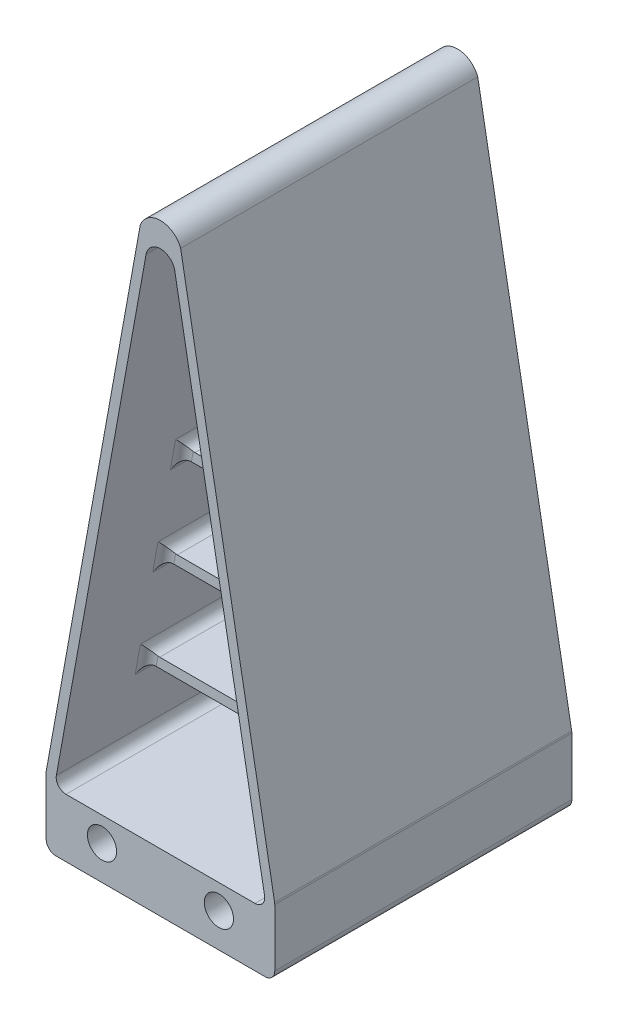
SolidWorks part; units mm, degrees
ref_plane "Front Plane" through (0, 0, 0) normal (0, 0, 1) x (1, 0, 0)
ref_plane "Top Plane" through (0, 0, 0) normal (0, 1, 0) x (1, 0, 0)
ref_plane "Right Plane" through (0, 0, 0) normal (1, 0, 0) x (0, 0, -1)
sketch "Sketch1" plane through (0, 0, 0) normal (0, 0, 1) x (1, 0, 0)
  line L0 (-0.246, 29.2945) -> (-1.0225, 25) construction
  line L1 (1.0225, 25) -> (0.246, 29.2945) construction
  line L2 (-1.0225, 25) -> (1.0225, 25) construction
  line L3 (1.2034, 24) -> (-1.2034, 24) construction
  line L4 (-1.2034, 24) -> (-2.8307, 15) construction
  line L5 (-2.8307, 15) -> (-1.0115, 15) construction
  line L6 (-1.0115, 15) -> (-1.0115, 15.5) construction
  line L7 (-1.0115, 15.5) -> (1.0115, 15.5) construction
  line L8 (2.8307, 15) -> (1.2034, 24) construction
  line L9 (1.0115, 15.5) -> (1.0115, 15) construction
  line L10 (1.0115, 15) -> (2.8307, 15) construction
  line L11 (3.0115, 14) -> (1.0115, 14) construction
  line L12 (1.0115, 14) -> (1.0115, 13.5) construction
  line L13 (1.0115, 13.5) -> (-1.0115, 13.5) construction
  line L14 (-1.0115, 13.5) -> (-1.0115, 14) construction
  line L15 (-1.0115, 14) -> (-3.0115, 14) construction
  line L16 (-3.0115, 14) -> (-4.6389, 5) construction
  line L17 (-4.6389, 5) -> (-2.8197, 5) construction
  line L18 (-2.8197, 5) -> (-2.8197, 5.5) construction
  line L19 (-2.8197, 5.5) -> (2.8197, 5.5) construction
  line L20 (2.8197, 5.5) -> (2.8197, 5) construction
  line L21 (2.8197, 5) -> (4.6389, 5) construction
  line L22 (4.6389, 5) -> (3.0115, 14) construction
  line L23 (4.8197, 4) -> (2.8197, 4) construction
  line L24 (2.8197, 4) -> (2.8197, 3.5) construction
  line L25 (2.8197, 3.5) -> (-2.8197, 3.5) construction
  line L26 (-2.8197, 3.5) -> (-2.8197, 4) construction
  line L27 (-2.8197, 4) -> (-4.8197, 4) construction
  line L28 (-4.8197, 4) -> (-6.4471, -5) construction
  line L29 (-6.4471, -5) -> (-4.6279, -5) construction
  line L30 (-4.6279, -5) -> (-4.6279, -4.5) construction
  line L31 (-4.6279, -4.5) -> (4.6279, -4.5) construction
  line L32 (4.6279, -4.5) -> (4.6279, -5) construction
  line L33 (6.4471, -5) -> (4.8197, 4) construction
  line L34 (4.6279, -5) -> (6.4471, -5) construction
  line L35 (6.6279, -6) -> (4.6279, -6) construction
  line L36 (4.6279, -6) -> (4.6279, -6.5) construction
  line L37 (4.6279, -6.5) -> (-4.6279, -6.5) construction
  line L38 (-4.6279, -6.5) -> (-4.6279, -6) construction
  line L39 (-4.6279, -6) -> (-6.6279, -6) construction
  line L40 (-6.6279, -6) -> (-8.2553, -15) construction
  line L41 (-6.4361, -16) -> (-8.4361, -16) construction
  line L42 (-8.2553, -15) -> (-6.4361, -15) construction
  line L43 (-6.4361, -15) -> (-6.4361, -14.5) construction
  line L44 (-6.4361, -16.5) -> (-6.4361, -16) construction
  line L45 (6.4361, -16.5) -> (-6.4361, -16.5) construction
  line L46 (-6.4361, -14.5) -> (6.4361, -14.5) construction
  line L47 (6.4361, -14.5) -> (6.4361, -15) construction
  line L48 (6.4361, -16) -> (6.4361, -16.5) construction
  line L49 (8.4361, -16) -> (6.4361, -16) construction
  line L50 (8.2553, -15) -> (6.6279, -6) construction
  line L51 (6.4361, -15) -> (8.2553, -15) construction
  line L52 (10.0635, -25) -> (8.4361, -16) construction
  line L53 (9.7018, -23) -> (-9.7018, -23)
  line L54 (2.2141, 29.6504) -> (2.0739, 30.4257)
  line L55 (-2.2141, 29.6504) -> (-2.0739, 30.4257)
  line L56 (0.246, 29.2945) -> (0, 30.655)
  line L57 (-0.246, 29.2945) -> (0, 30.655)
  line L59 (-8.4361, -16) -> (-10.0635, -25) construction
  line L68 (13, -30) -> (2.2141, 29.6504) construction
  line L69 (-2.2141, 29.6504) -> (-13, -30) construction
  line L70 (-0.246, 29.2945) -> (-1.0225, 25)
  line L71 (1.0225, 25) -> (0.246, 29.2945)
  line L72 (-1.0225, 25) -> (1.0225, 25)
  line L73 (1.2034, 24) -> (-1.2034, 24)
  line L74 (-1.2034, 24) -> (-2.8307, 15)
  line L75 (-2.8307, 15) -> (-1.0115, 15)
  line L76 (-1.0115, 15) -> (-1.0115, 15.5)
  line L77 (-1.0115, 15.5) -> (1.0115, 15.5)
  line L78 (2.8307, 15) -> (1.2034, 24)
  line L79 (1.0115, 15.5) -> (1.0115, 15)
  line L80 (1.0115, 15) -> (2.8307, 15)
  line L81 (3.0115, 14) -> (1.0115, 14)
  line L82 (1.0115, 14) -> (1.0115, 13.5)
  line L83 (1.0115, 13.5) -> (-1.0115, 13.5)
  line L84 (-1.0115, 13.5) -> (-1.0115, 14)
  line L85 (-1.0115, 14) -> (-3.0115, 14)
  line L86 (-3.0115, 14) -> (-4.6389, 5)
  line L87 (-4.6389, 5) -> (-2.8197, 5)
  line L88 (-2.8197, 5) -> (-2.8197, 5.5)
  line L89 (-2.8197, 5.5) -> (2.8197, 5.5)
  line L90 (2.8197, 5.5) -> (2.8197, 5)
  line L91 (2.8197, 5) -> (4.6389, 5)
  line L92 (4.6389, 5) -> (3.0115, 14)
  line L93 (4.8197, 4) -> (2.8197, 4)
  line L94 (2.8197, 4) -> (2.8197, 3.5)
  line L95 (2.8197, 3.5) -> (-2.8197, 3.5)
  line L96 (-2.8197, 3.5) -> (-2.8197, 4)
  line L97 (-2.8197, 4) -> (-4.8197, 4)
  line L98 (-4.8197, 4) -> (-6.4471, -5)
  line L99 (-6.4471, -5) -> (-4.6279, -5)
  line L100 (-4.6279, -5) -> (-4.6279, -4.5)
  line L101 (-4.6279, -4.5) -> (4.6279, -4.5)
  line L102 (4.6279, -4.5) -> (4.6279, -5)
  line L103 (6.4471, -5) -> (4.8197, 4)
  line L104 (4.6279, -5) -> (6.4471, -5)
  line L105 (6.6279, -6) -> (4.6279, -6)
  line L106 (4.6279, -6) -> (4.6279, -6.5)
  line L107 (4.6279, -6.5) -> (-4.6279, -6.5)
  line L108 (-4.6279, -6.5) -> (-4.6279, -6)
  line L109 (-4.6279, -6) -> (-6.6279, -6)
  line L110 (-6.6279, -6) -> (-8.2553, -15)
  line L111 (-6.4361, -16) -> (-8.4361, -16)
  line L112 (-8.2553, -15) -> (-6.4361, -15)
  line L113 (-6.4361, -15) -> (-6.4361, -14.5)
  line L114 (-6.4361, -16.5) -> (-6.4361, -16)
  line L115 (6.4361, -16.5) -> (-6.4361, -16.5)
  line L116 (-6.4361, -14.5) -> (6.4361, -14.5)
  line L117 (6.4361, -14.5) -> (6.4361, -15)
  line L118 (6.4361, -16) -> (6.4361, -16.5)
  line L119 (8.4361, -16) -> (6.4361, -16)
  line L120 (8.2553, -15) -> (6.6279, -6)
  line L121 (6.4361, -15) -> (8.2553, -15)
  line L122 (9.7018, -23) -> (8.4361, -16)
  line L129 (-8.4361, -16) -> (-9.7018, -23)
  line L138 (11.7343, -23) -> (2.2141, 29.6504)
  line L139 (-2.2141, 29.6504) -> (-11.7343, -23)
  line L141 (-11.7343, -30) -> (11.7343, -30)
  line L142 (11.7343, -23) -> (11.7343, -30)
  line L143 (-11.7343, -23) -> (-11.7343, -30)
  arc A6 (2.0739, 30.4257) -> (-2.0739, 30.4257) centre (0, 29.6504) ccw
  dimension "D1" = 2
  dimension "D2" = 7
extrude "Boss-Extrude1" add sketch "Sketch1" along normal blind 30.5
fillet "Fillet1" radius 1 4 edges at (-11.7343, -23, 15.25) (11.7343, -23, 15.25) (-9.7018, -23, 15.25) (9.7018, -23, 15.25)
fillet "Fillet2" radius 0.5 20 edges at (8.2553, -15, 15.25) (6.4471, -5, 15.25) (4.6389, 5, 15.25) (2.8307, 15, 15.25) (1.0225, 25, 15.25) (-8.2553, -15, 15.25) (-6.4471, -5, 15.25) (-4.6389, 5, 15.25) (-2.8307, 15, 15.25) (-1.0225, 25, 15.25) (-1.2034, 24, 15.25) (-3.0115, 14, 15.25) (-4.8197, 4, 15.25) (-6.6279, -6, 15.25) (-8.4361, -16, 15.25) (1.2034, 24, 15.25) (3.0115, 14, 15.25) (4.8197, 4, 15.25) (6.6279, -6, 15.25) (8.4361, -16, 15.25)
hole_wizard "Ø3.0 (3) Diameter Hole1" positions "Sketch4" profile "Sketch3" hole size "Ø3.0" standard "DIN" end condition through all
sketch "Sketch4" plane through (0, 0, 0) normal (0, 0, -1) x (-1, 0, 0)
  line L0 (11.7343, -30) -> (-11.7343, -30) construction
  point P0 (-6, -26.5)
  point P2 (6, -26.5)
  point P11 (0, -30)
  dimension "D1" = 3.5
  dimension "D2" = 12
  dimension "D3" = 6
sketch "Sketch3" plane through (6, -26.5, 0) normal (1, 0, 0) x (0, 1, 0)
  line L0 (0, 0) -> (0, 30.5)
  line L1 (0, 30.5) -> (1.5, 30.5)
  line L2 (1.5, 30.5) -> (1.5, 0)
  line L5 (1.5, 0) -> (0, 0)
  line L11 (0, -6.35) -> (0, 107.95) construction
  dimension "Thru Hole Dia." = 3
  dimension "Thru Hole Depth" = 30.5
sketch "Sketch5" plane through (0, 0, 0) normal (0, 0, -1) x (-1, 0, 0)
  line L0 (-0.916, 25.589) -> (-1.2987, 23.4725)
  line L1 (-2.7242, 15.589) -> (-1.2777, 23.589) construction
  line L2 (-1.2987, 23.4725) -> (1.364, 23.1113)
  line L3 (1.2777, 23.589) -> (2.7242, 15.589) construction
  line L4 (1.364, 23.1113) -> (0.8313, 26.0576)
  line L5 (0, 30.655) -> (0.916, 25.589) construction
  line L6 (0.8313, 26.0576) -> (-0.916, 25.589)
extrude "Cut-Extrude1" cut sketch "Sketch5" against normal blind 52
sketch "Sketch6" plane through (7.3356, 1.3264, 0) normal (0.984, 0.1779, 0) x (0, 0, -1)
  line L0 (-30.5, -24.6312) -> (-30.5, 29.5712) construction
  line L1 (-5, 25.5712) -> (-25.5, 15.5712) construction
  line L2 (-25.5, 0.5712) -> (-5, 0.5712) construction
  line L3 (-25.5, 25.5712) -> (-5, 25.5712) construction
  line L4 (-25.5, 25.5712) -> (-5, 15.5712) construction
  line L5 (0, -24.6312) -> (0, 29.5712) construction
  line L6 (-25.5, 15.5712) -> (-5, 15.5712) construction
  line L7 (-25.5, 25.5712) -> (-5, 25.5712) construction
  line L8 (-25.5, 25.5712) -> (-25.5, 15.5712) construction
  line L9 (-25.5, 15.5712) -> (-5, 15.5712) construction
  line L10 (-5, 25.5712) -> (-5, 15.5712) construction
  line L11 (-5, 0.5712) -> (-5, -9.4288) construction
  line L12 (-5, -9.4288) -> (-25.5, 0.5712) construction
  line L13 (-25.5, 0.5712) -> (-25.5, -9.4288) construction
  line L14 (-25.5, 5.5712) -> (-5, 5.5712) construction
  line L15 (-25.5, -9.4288) -> (-5, 0.5712) construction
  line L16 (-25.5, -9.4288) -> (-5, -9.4288) construction
  line L17 (-15.25, 15.5712) -> (-15.25, 0.5712) construction
  circle A0 centre (-25.5, 25.5712) radius 1.5
  circle A1 centre (-5, 25.5712) radius 1.5
  circle A3 centre (-5, 15.5712) radius 1.5
  circle A4 centre (-25.5, 15.5712) radius 1.5
  circle A5 centre (-25.5, 15.5712) radius 1.5
  circle A6 centre (-5, 15.5712) radius 1.5
  circle A15 centre (-15.25, 20.5712) radius 1.5
  circle A16 centre (-5, 5.5712) radius 1.5 [skipped]
  circle A17 centre (-25.5, 5.5712) radius 1.5 [skipped]
  circle A18 centre (-25.5, 5.5712) radius 1.5 [skipped]
  circle A19 centre (-5, 5.5712) radius 1.5 [skipped]
  circle A20 centre (-15.25, -4.4288) radius 1.5
  circle A21 centre (-5, -4.4288) radius 1.5 [skipped]
  circle A22 centre (-25.5, -4.4288) radius 1.5 [skipped]
  circle A25 centre (-25.5, 0.5712) radius 1.5
  circle A26 centre (-5, 0.5712) radius 1.5
  circle A27 centre (-25.5, -9.4288) radius 1.5
  circle A28 centre (-5, -9.4288) radius 1.5
  circle A29 centre (-15.25, 8.0712) radius 1.5
  dimension "D1" = 3
  dimension "D2" = 3
  dimension "D3" = 5
  dimension "D5" = 3
  dimension "D6" = 2
  dimension "D4" = 5
  dimension "D7" = 3
extrude "Boss-Extrude2" add sketch "Sketch6" along normal blind 2 contours A0 | A1 | A3 | A26 | A25 | A27 | A28 | A4 | A15 | A20 | A29 region at (2.7856, 26.4895, 25.5) region at (2.7856, 26.4895, 5) region at (4.565, 16.6491, 5) region at (7.234, 1.8885, 25.5) region at (7.234, 1.8885, 5) region at (9.0133, -7.952, 25.5) region at (9.0133, -7.952, 5)
fillet "Fillet3" radius 1 9 edges at (3.0525, 25.0135, 5) (4.2981, 18.1252, 5) (7.5009, 0.4124, 5) (7.5009, 0.4124, 25.5) (8.7464, -6.4759, 25.5) (8.7464, -6.4759, 5) (4.8319, 15.173, 25.5) (3.0525, 25.0135, 25.5) (6.1664, 7.7927, 15.25)
fillet "Fillet4" radius 1 9 edges at (6.8, 15.5289, 25.5) (10.7145, -6.12, 5) (10.7145, -6.12, 25.5) (8.9352, 3.7204, 25.5) (8.9352, 3.7204, 5) (6.2662, 18.481, 5) (4.4868, 28.3215, 5) (4.4868, 28.3215, 25.5) (7.6007, 11.1007, 15.25)
fillet "Fillet7" radius 1 16 edges at (6.4361, -16, 15.25) (-6.4361, -16, 15.25) (6.4361, -15, 15.25) (-6.4361, -15, 15.25) (-4.6279, -6, 15.25) (4.6279, -6, 15.25) (4.6279, -5, 15.25) (-4.6279, -5, 15.25) (-2.8197, 4, 15.25) (2.8197, 4, 15.25) (2.8197, 5, 15.25) (-2.8197, 5, 15.25) (-1.0115, 14, 15.25) (1.0115, 14, 15.25) (-1.0115, 15, 15.25) (1.0115, 15, 15.25)
fillet "Fillet8" radius 1 18 edges at (6.4361, -16.5, 15.25) (-6.4361, -16.5, 15.25) (4.6279, -6.5, 15.25) (-4.6279, -6.5, 15.25) (-6.4361, -14.5, 15.25) (6.4361, -14.5, 15.25) (2.8197, 3.5, 15.25) (-2.8197, 3.5, 15.25) (-4.6279, -4.5, 15.25) (4.6279, -4.5, 15.25) (1.0115, 13.5, 15.25) (-1.0115, 13.5, 15.25) (-2.8197, 5.5, 15.25) (2.8197, 5.5, 15.25) (11.7343, -30, 15.25) (-11.7343, -30, 15.25) (-1.0115, 15.5, 15.25) (1.0115, 15.5, 15.25)
fillet "Fillet9" radius 0.5 1 edges at (0, 30.655, 15.25)
fillet "Fillet10" radius 1 4 edges at (8.3905, -4.5078, 15.25) (9.8248, -1.1998, 15.25) (5.3765, 23.4012, 15.25) (3.9422, 20.0933, 15.25)
sketch "Sketch7" plane through (7.3356, 1.3264, 0) normal (0.984, 0.1779, 0) x (0, 0, -1)
  line L0 (-15.25, 20.5712) -> (-15.25, -4.4288) construction
  line L9 (-11.75, -21.4288) -> (-11.75, -7.2573)
  line L10 (-18.75, 3.5712) -> (-11.75, 3.5712)
  line L11 (-18.75, 3.5712) -> (-18.75, 17.7427)
  line L13 (-11.75, 3.5712) -> (-11.75, 17.7427)
  line L14 (-18.75, 3.5712) -> (-11.75, 18.5712) construction
  line L15 (-18.75, 18.5712) -> (-11.75, 3.5712) construction
  line L16 (-18.75, -21.4288) -> (-18.75, -7.2573)
  line L17 (-18.75, -21.4288) -> (-11.75, -21.4288)
  arc A2 (-11.75, 17.7427) -> (-18.75, 17.7427) centre (-15.25, 20.5712) ccw
  arc A4 (-11.75, -7.2573) -> (-18.75, -7.2573) centre (-15.25, -4.4288) ccw
  point P4 (-15.25, 11.0712)
  dimension "D1" = 9
  dimension "D2" = 7
  dimension "D3" = 15
  dimension "D4" = 9.5
  dimension "D5" = 2
extrude "Cut-Extrude2" [suppressed] cut sketch "Sketch7" along normal blind 5 and the other way blind 1
fillet "Fillet11" [suppressed] radius 1
sketch "Sketch8" [suppressed] plane through (7.3356, 1.3264, 0) normal (0.984, 0.1779, 0) x (0, 0, -1)
  line L0 (-17.75, 4.5712) -> (-18.4571, 3.8641)
  line L1 (-18.4571, 3.8641) -> (-20.6603, 1.6608)
  line L2 (-20.6603, 1.6608) -> (-21.1468, 1.1744)
  line L3 (-21.1468, 1.1744) -> (-21.1468, -24.6312)
  line L4 (-30.5, -24.6312) -> (0, -24.6312) construction
  line L5 (-15.25, 3.5712) -> (-15.25, 0.0712) construction
  line L6 (-12.75, 3.5712) -> (-17.75, 3.5712) construction
  line L7 (-17.1843, 4.0055) -> (-17.8914, 3.2984)
  line L8 (-17.8914, 3.2984) -> (-20.0947, 1.0951)
  line L9 (-20.0947, 1.0951) -> (-20.3468, 0.843)
  line L10 (-20.3468, 0.843) -> (-20.3468, -24.6312)
  line L11 (-18.3157, 5.1369) -> (-19.0228, 4.4297)
  line L12 (-19.0228, 4.4297) -> (-21.226, 2.2265)
  line L13 (-21.226, 2.2265) -> (-21.9468, 1.5058)
  line L14 (-21.9468, 1.5058) -> (-21.9468, -24.6312)
  line L15 (-8.5532, 1.5058) -> (-8.5532, -24.6312)
  line L16 (-9.274, 2.2265) -> (-8.5532, 1.5058)
  line L17 (-11.4772, 4.4297) -> (-9.274, 2.2265)
  line L18 (-12.1843, 5.1369) -> (-11.4772, 4.4297)
  line L19 (-10.1532, 0.843) -> (-10.1532, -24.6312)
  line L20 (-10.4053, 1.0951) -> (-10.1532, 0.843)
  line L21 (-12.6086, 3.2984) -> (-10.4053, 1.0951)
  line L22 (-13.3157, 4.0055) -> (-12.6086, 3.2984)
  line L23 (-9.3532, 1.1744) -> (-9.3532, -24.6312)
  line L24 (-9.8397, 1.6608) -> (-9.3532, 1.1744)
  line L25 (-12.0429, 3.8641) -> (-9.8397, 1.6608)
  line L26 (-12.75, 4.5712) -> (-12.0429, 3.8641)
  arc A0 (-18.75, 4.5712) -> (-17.75, 3.5712) centre (-17.75, 4.5712) ccw construction
  arc A1 (-11.5682, -7.0162) -> (-18.9318, -7.0162) centre (-15.25, -4.4288) ccw construction
  arc A2 (-17.1843, 4.0055) -> (-18.3157, 5.1369) centre (-17.75, 4.5712) ccw
  arc A3 (-20.3468, -24.6312) -> (-21.9468, -24.6312) centre (-21.1468, -24.6312) cw
  arc A4 (-10.1532, -24.6312) -> (-8.5532, -24.6312) centre (-9.3532, -24.6312) ccw
  arc A5 (-13.3157, 4.0055) -> (-12.1843, 5.1369) centre (-12.75, 4.5712) cw
  line M6 (-18.75, 4.5712) -> (-18.75, 17.4089)
  line M10 (-11.75, 17.4089) -> (-11.75, 4.5712)
  arc M11 (-11.75, 4.5712) -> (-12.75, 3.5712) centre (-12.75, 4.5712) cw
  line M12 (-12.75, 3.5712) -> (-17.75, 3.5712)
  arc M13 (-17.75, 3.5712) -> (-18.75, 4.5712) centre (-17.75, 4.5712) cw
  line M31 (-30.5, -24.6312) -> (0, -24.6312)
  dimension "D1" = 0.8
  dimension "D2" = 0.8
extrude "Cut-Extrude3" [suppressed] cut sketch "Sketch8" against normal blind 1 contours L7 A2 L11 M6 M13 M12 | L13 L14 L3 L2 L1 L11 L12 M31 M13 M6 | L10 L9 L8 L7 L1 L2 L3 M12 M13 M31 | A5 L22 L18 M12 M11 M10 | L25 L24 L23 L15 L16 L17 L18 M11 M31 M10 | L25 L22 L21 L20 L19 L23 L24 M11 M12 M31
fillet "Fillet12" [suppressed] radius 1
sketch "Sketch9" [suppressed] plane through (7.3356, 1.3264, 0) normal (0.984, 0.1779, 0) x (0, 0, -1)
  line L0 (-30.5, -24.6312) -> (0, -24.6312) construction
  line L1 (-17.75, -21.4288) -> (-16.15, -21.4288)
  line L2 (-17.75, -21.4288) -> (-17.75, -24.6312)
  line L3 (-17.75, -24.6312) -> (-16.15, -24.6312)
  line L4 (-16.15, -21.4288) -> (-16.15, -24.6312)
  line L6 (-12.75, -21.4288) -> (-14.35, -21.4288)
  line L7 (-12.75, -21.4288) -> (-12.75, -24.6312)
  line L8 (-12.75, -24.6312) -> (-14.35, -24.6312)
  line L9 (-14.35, -21.4288) -> (-14.35, -24.6312)
  dimension "D1" = 1.6
  dimension "D2" = 1.6
extrude "Cut-Extrude4" [suppressed] cut sketch "Sketch9" against normal blind 1
fillet "Fillet13" [suppressed] radius 1
sketch "Sketch10" [suppressed] plane through (4.3827, -24.2382, 0) normal (-0.1779, 0.984, 0) x (0.984, 0.1779, 0)
  line L1 (7.4546, -8.5532) -> (6.4546, -8.5532)
  line L2 (7.4546, -8.5532) -> (7.4546, -10.1532)
  line L3 (7.4546, -10.1532) -> (6.4546, -10.1532)
  line L4 (6.4546, -8.5532) -> (6.4546, -10.1532)
  line L5 (7.4546, -12.75) -> (6.4546, -12.75)
  line L6 (7.4546, -12.75) -> (7.4546, -14.35)
  line L7 (7.4546, -14.35) -> (6.4546, -14.35)
  line L8 (6.4546, -12.75) -> (6.4546, -14.35)
  line L9 (7.4546, -16.15) -> (6.4546, -16.15)
  line L10 (7.4546, -16.15) -> (7.4546, -17.75)
  line L11 (7.4546, -17.75) -> (6.4546, -17.75)
  line L12 (6.4546, -16.15) -> (6.4546, -17.75)
  line L13 (7.4546, -20.3468) -> (6.4546, -20.3468)
  line L14 (7.4546, -20.3468) -> (7.4546, -21.9468)
  line L15 (7.4546, -21.9468) -> (6.4546, -21.9468)
  line L16 (6.4546, -20.3468) -> (6.4546, -21.9468)
extrude "Cut-Extrude5" [suppressed] cut sketch "Sketch10" against normal blind 19
sketch "Sketch16" plane through (0, 0, 0) normal (0, 0, -1) x (-1, 0, 0)
  line L3 (-5.6551, 5) -> (5.6551, 5)
  line L6 (-3.7083, 15.7669) -> (-1.4761, 28.1119)
  line L7 (1.4761, 28.1119) -> (3.7083, 15.7669)
  line L8 (-3.8469, 15) -> (-1.4761, 28.1119)
  line L9 (1.4761, 28.1119) -> (3.8469, 15)
  line L11 (-3.8469, 15) -> (3.8469, 15)
  line L12 (4.0278, 14) -> (-4.0278, 14)
  line L13 (-5.8359, 4) -> (-7.4633, -5)
  line L14 (5.8359, 4) -> (7.4633, -5)
  line L15 (5.8359, 4) -> (-5.8359, 4)
  line L16 (7.4633, -5) -> (-7.4633, -5)
  line L17 (9.2715, -15) -> (-9.2715, -15)
  line L18 (-9.4523, -16) -> (9.4523, -16)
  line L19 (-9.4523, -16) -> (-10.8989, -24)
  line L20 (9.4523, -16) -> (10.8989, -24)
  line L21 (-7.6441, -6) -> (7.6441, -6)
  line L22 (-7.6441, -6) -> (-9.2715, -15)
  line L23 (7.6441, -6) -> (9.2715, -15)
  line L24 (-10.8989, -24) -> (10.8989, -24)
  line L25 (8.5048, -23) -> (-8.5048, -23) construction
  line L101 (3.6858, 4) -> (4.0404, 4)
  line L102 (-2.3629, 4.5) -> (2.3629, 4.5)
  line L103 (-4.0404, 4) -> (-3.6858, 4)
  line L104 (-1.8776, 15) -> (-2.5938, 15)
  line L105 (0.5547, 14.5) -> (-0.5547, 14.5)
  line L106 (5.5165, 5.7669) -> (4.0699, 13.7669)
  line L107 (-4.0699, 13.7669) -> (-5.5165, 5.7669)
  line L113 (5.6551, 5) -> (4.0278, 14)
  line L114 (-4.0278, 14) -> (-5.6551, 5)
  arc A3 (1.4761, 28.1119) -> (-1.4761, 28.1119) centre (0, 27.845) ccw
  arc A4 (1.4761, 28.1119) -> (-1.4761, 28.1119) centre (0, 27.845) ccw
  arc A136 (4.0404, 4) -> (5.5165, 5.7669) centre (4.0404, 5.5) ccw
  arc A137 (2.3629, 4.5) -> (3.6858, 4) centre (3.6858, 6) ccw
  arc A138 (-3.6858, 4) -> (-2.3629, 4.5) centre (-3.6858, 6) ccw
  arc A139 (-5.5165, 5.7669) -> (-4.0404, 4) centre (-4.0404, 5.5) ccw
  arc A140 (-2.5938, 15) -> (-4.0699, 13.7669) centre (-2.5938, 13.5) ccw
  arc A141 (-0.5547, 14.5) -> (-1.8776, 15) centre (-1.8776, 13) ccw
  arc A142 (1.8776, 15) -> (0.5547, 14.5) centre (1.8776, 13) ccw
  arc A143 (4.0699, 13.7669) -> (2.5938, 15) centre (2.5938, 13.5) ccw
  dimension "D3" = 1
  dimension "D1" = 1
  dimension "D2" = 1
extrude "Cut-Extrude9" cut sketch "Sketch16" against normal blind 41
fillet "Fillet19" radius 1 18 edges at (-3.8469, 15, 15.25) (3.8469, 15, 15.25) (-7.4633, -5, 15.25) (7.4633, -5, 15.25) (5.8359, 4, 15.25) (-5.8359, 4, 15.25) (4.0278, 14, 15.25) (-4.0278, 14, 15.25) (-5.6551, 5, 15.25) (5.6551, 5, 15.25) (-9.2715, -15, 15.25) (9.2715, -15, 15.25) (7.6441, -6, 15.25) (-7.6441, -6, 15.25) (10.8989, -24, 15.25) (9.4523, -16, 15.25) (-9.4523, -16, 15.25) (-10.8989, -24, 15.25)
sketch "Sketch17" plane through (0, 0, 0) normal (0, 0, -1) x (-1, 0, 0)
  line L3 (-3.6339, 16.1779) -> (-10.6859, -22.8221)
  line L4 (-9.7018, -24) -> (9.7018, -24)
  line L5 (-1.4761, 28.1119) -> (-3.6339, 16.1779)
  line L6 (3.6339, 16.1779) -> (1.4761, 28.1119)
  line L7 (-1.4761, 28.1119) -> (-3.6339, 16.1779)
  line L8 (3.6339, 16.1779) -> (1.4761, 28.1119)
  line L9 (3.6339, 16.1779) -> (10.6859, -22.8221)
  arc A3 (-10.6859, -22.8221) -> (-9.7018, -24) centre (-9.7018, -23) ccw
  arc A4 (1.4761, 28.1119) -> (-1.4761, 28.1119) centre (0, 27.845) ccw
  arc A5 (1.4761, 28.1119) -> (-1.4761, 28.1119) centre (0, 27.845) ccw
  arc A6 (9.7018, -24) -> (10.6859, -22.8221) centre (9.7018, -23) ccw
  arc A7 (9.7018, -24) -> (10.6859, -22.8221) centre (9.7018, -23) ccw construction
  dimension "D1" = 0
extrude "Cut-Extrude10" cut sketch "Sketch17" against normal blind 8
fillet "Fillet20" radius 1 8 edges at (-3.9052, 14.6779, 8) (-5.7134, 4.6779, 8) (-7.5215, -5.3221, 8) (-9.3297, -15.3221, 8) (9.3297, -15.3221, 8) (7.5215, -5.3221, 8) (5.7134, 4.6779, 8) (3.9052, 14.6779, 8)
ref_plane "Plane2" through (0, 0, 15.25) normal (0, 0, -1) x (-1, 0, 0)
mirror "Mirror2" about plane through (0, 0, 15.25) normal (0, 0, -1) of "Fillet20", "Cut-Extrude10"
sketch "Sketch18" plane through (7.3356, 1.3264, 0) normal (0.984, 0.1779, 0) x (0, 0, -1)
  line L1 (-30.5, 29.5712) -> (0, 29.5712)
  line L2 (-30.5, 29.5712) -> (-30.5, -21.8907)
  line L3 (-30.5, -21.8907) -> (0, -21.8907)
  line L4 (0, 29.5712) -> (0, -21.8907)
extrude "Cut-Extrude11" cut sketch "Sketch18" along normal blind 10
